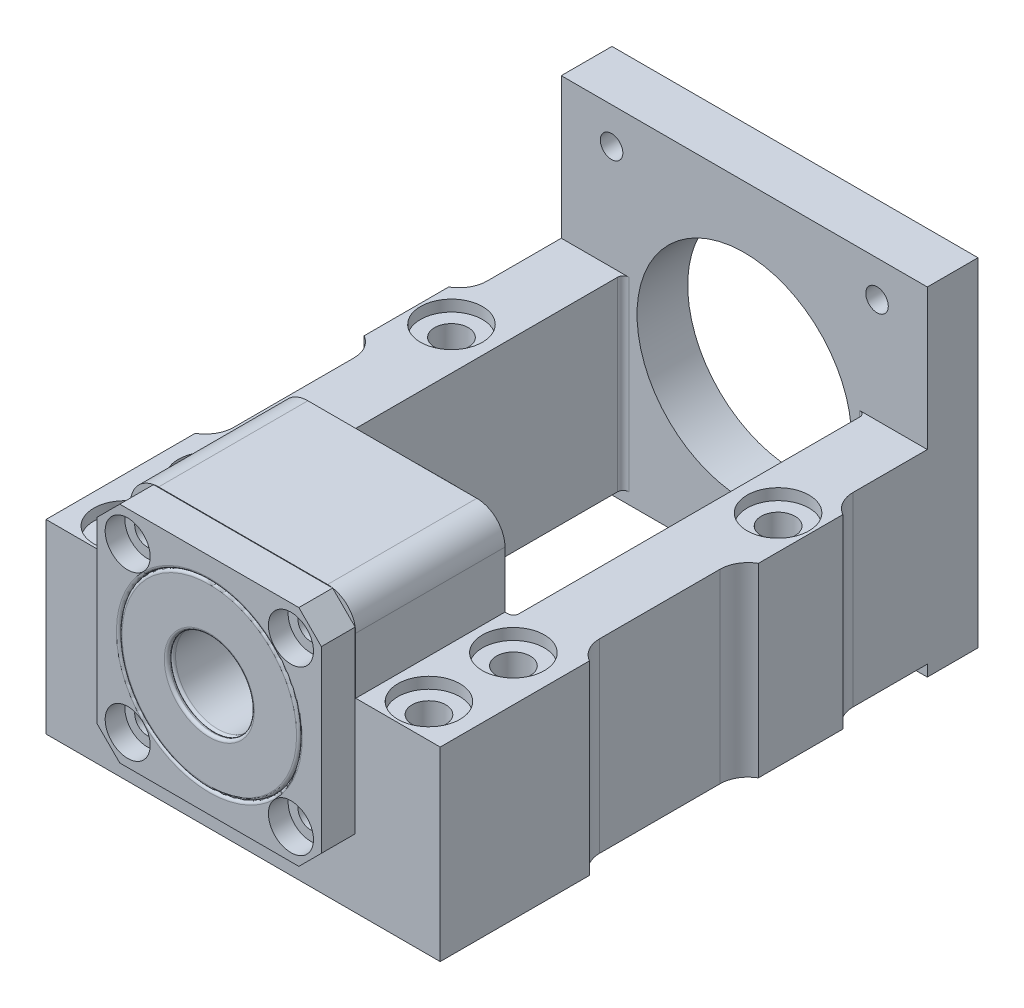
SolidWorks part; units mm, degrees
other "Camera1"
material "Gray Cast Iron"
ref_plane "Front Plane" through (0, 0, 0) normal (0, 0, 1) x (1, 0, 0)
ref_plane "Top Plane" through (0, 0, 0) normal (0, 1, 0) x (1, 0, 0)
ref_plane "Right Plane" through (0, 0, 0) normal (1, 0, 0) x (0, 0, -1)
sketch "Sketch1" plane through (0, 0, 0) normal (0, 0, 1) x (1, 0, 0)
  line L0 (-35, 0) -> (35, 0) construction
  line L1 (0, 0) -> (0, -28) construction
  line L2 (-35, -28) -> (35, -28)
  line L3 (-35, 0) -> (-35, -28)
  line L4 (35, 0) -> (35, -28)
  line L5 (-35, 5) -> (-35, 0)
  line L12 (-35, 5) -> (35, 5)
  line L13 (35, 5) -> (35, 0)
  point P4 (0, 0)
  point P10 (0, -28)
  dimension "D1" = 70
  dimension "D2" = 28
  dimension "D3" = 33
extrude "Boss-Extrude1" add sketch "Sketch1" against normal blind 98
sketch "Sketch2" plane through (0, 5, 0) normal (0, 1, 0) x (1, 0, 0)
  line L0 (0, 98) -> (0, 108.2746) construction
  line L1 (35, 98) -> (-35, 98) construction
  line L2 (-29, 108.2746) -> (29, 108.2746) construction
  line L3 (-29, 108.2746) -> (-29, 66) construction
  line L5 (29, 108.2746) -> (29, 66) construction
  line L6 (-29, 66) -> (29, 66) construction
  line L7 (0, 0) -> (0, -10.7937) construction
  line L8 (-27, -10.7937) -> (27, -10.7937) construction
  line L9 (-27, -10.7937) -> (-27, 21) construction
  line L10 (-27, 21) -> (27, 21) construction
  line L11 (27, 21) -> (27, -10.7937) construction
  line L13 (-27, 6) -> (27, 6) construction
  circle A0 centre (-29, 66) radius 3
  circle A1 centre (29, 66) radius 3
  circle A6 centre (-27, 21) radius 3
  circle A7 centre (-27, 6) radius 3
  circle A8 centre (27, 21) radius 3
  circle A9 centre (27, 6) radius 3
  point P8 (0, 108.2746)
  point P15 (0, -10.7937)
  dimension "D5" = 6
  dimension "D1" = 58
  dimension "D2" = 32
  dimension "D3" = 54
  dimension "D4" = 45
  dimension "D6" = 15
extrude "Cut-Extrude1" cut sketch "Sketch2" against normal blind 50
sketch "Sketch3" plane through (0, 5, 0) normal (0, 1, 0) x (1, 0, 0)
  circle A0 centre (-29, 66) radius 5.5
  circle A1 centre (29, 66) radius 5.5
  circle A6 centre (-27, 21) radius 5.5
  circle A7 centre (-27, 6) radius 5.5
  circle A8 centre (27, 21) radius 5.5
  circle A9 centre (27, 6) radius 5.5
  dimension "D1" = 11
extrude "Cut-Extrude3" cut sketch "Sketch3" against normal blind 2
sketch "Sketch4" plane through (0, 0, -98) normal (0, 0, 1) x (1, 0, 0)
  line L0 (0, -30) -> (0, 30) construction
  line L1 (-32.5, -30) -> (32.5, -30)
  line L2 (-32.5, 30) -> (32.5, 30)
  line L3 (-32.5, 30) -> (-32.5, -30)
  line L4 (32.5, 30) -> (32.5, -30)
  point P4 (0, 0)
  point P7 (0, -30)
  dimension "D1" = 65
  dimension "D2" = 60
extrude "Boss-Extrude3" add sketch "Sketch4" along normal blind 9
sketch "Sketch5" plane through (0, 5, 0) normal (0, 1, 0) x (1, 0, 0)
  line L0 (-21.5, 26.5) -> (21.5, 26.5)
  line L1 (21.5, 26.5) -> (21.5, 89)
  line L2 (32.5, 89) -> (-32.5, 89) construction
  line L3 (-21.5, 26.5) -> (-21.5, 89)
  line L4 (-21.5, 89) -> (21.5, 89)
extrude "Cut-Extrude4" cut sketch "Sketch5" against normal blind 50
sketch "Sketch6" plane through (0, 0, 0) normal (0, 0, 1) x (1, 0, 0)
  line L0 (0, -20) -> (0, 20) construction
  line L1 (-20, 20) -> (20, 20)
  line L2 (-20, 20) -> (-20, -20)
  line L3 (-20, -20) -> (20, -20)
  line L4 (20, -20) -> (20, 20)
  point P4 (0, 0)
  point P8 (0, 20)
  dimension "D1" = 40
  dimension "D2" = 40
extrude "Boss-Extrude4" add sketch "Sketch6" against normal blind 26.5
sketch "Sketch7" plane through (0, 5, 0) normal (0, 1, 0) x (1, 0, 0)
  line L0 (-29, 71.5) -> (29, 71.5) construction
  line L2 (-29, 71.5) -> (-35, 71.5) construction
  line L3 (-35, 98) -> (-35, 0) construction
  line L4 (29, 71.5) -> (35, 71.5) construction
  line L5 (35, 98) -> (35, 0) construction
  line L6 (32.5, 98) -> (32.5, 71.5)
  line L7 (32.5, 71.5) -> (35, 71.5)
  line L8 (35, 71.5) -> (35, 98)
  line L9 (35, 98) -> (32.5, 98)
  line L10 (-35, 98) -> (-35, 71.5)
  line L11 (-35, 98) -> (-32.5, 98)
  line L12 (-32.5, 98) -> (-32.5, 71.5)
  line L13 (-32.5, 71.5) -> (-35, 71.5)
  line L14 (-27, 26.5) -> (27, 26.5) construction
  line L15 (27, 26.5) -> (35, 26.5) construction
  line L16 (-27, 26.5) -> (-35, 26.5) construction
  line L17 (32.5, 26.5) -> (32.5, 56.5)
  line L18 (32.5, 56.5) -> (35, 56.5)
  line L19 (35, 56.5) -> (35, 26.5)
  line L20 (35, 26.5) -> (32.5, 26.5)
  line L21 (-32.5, 26.5) -> (-32.5, 56.5)
  line L22 (-32.5, 56.5) -> (-35, 56.5)
  line L23 (-35, 56.5) -> (-35, 26.5)
  line L24 (-35, 26.5) -> (-32.5, 26.5)
  line L25 (-32.5, 56.5) -> (32.5, 56.5) construction
  circle A0 centre (-29, 66) radius 5.5 construction
  circle A1 centre (-29, 66) radius 5.5 construction
  circle A2 centre (29, 66) radius 5.5 construction
  circle A3 centre (-27, 21) radius 5.5 construction
  circle A4 centre (-27, 21) radius 5.5 construction
  circle A5 centre (27, 21) radius 5.5 construction
  circle A6 centre (27, 21) radius 5.5 construction
  dimension "D1" = 30
extrude "Cut-Extrude5" cut sketch "Sketch7" against normal blind 50
fillet "Fillet1" radius 5 6 edges at (32.5, -11.5, -71.5) (32.5, -11.5, -56.5) (32.5, -11.5, -26.5) (-32.5, -11.5, -26.5) (-32.5, -11.5, -56.5) (-32.5, -11.5, -71.5)
sketch "Sketch8" plane through (0, 0, -98) normal (0, 0, 1) x (1, 0, 0)
  circle A0 centre (0, 0) radius 19.05
  dimension "D1" = 38.1
extrude "Cut-Extrude6" cut sketch "Sketch8" along normal blind 10
sketch "Sketch9" plane through (0, 0, 0) normal (0, 0, 1) x (1, 0, 0)
  line L0 (0, -19.9) -> (0, 19.9) construction
  line L1 (-19.9, 19.9) -> (19.9, 19.9)
  line L2 (-19.9, 19.9) -> (-19.9, -19.9)
  line L3 (-19.9, -19.9) -> (19.9, -19.9)
  line L4 (19.9, -19.9) -> (19.9, 19.9)
  point P4 (0, 0)
  point P8 (0, 19.9)
  dimension "D1" = 39.8
  dimension "D2" = 39.8
extrude "Boss-Extrude5" add sketch "Sketch9" along normal blind 6 separate body
sketch "Sketch10" plane through (0, 0, -26.5) normal (0, 0, 1) x (1, 0, 0)
  circle A0 centre (0, 0) radius 16
  dimension "D1" = 32
extrude "Cut-Extrude7" cut sketch "Sketch10" along normal blind 50
fillet "Fillet2" radius 1 4 edges at (21.5, -11.5, -26.5) (-21.5, -11.5, -26.5) (-21.5, -11.5, -89) (21.5, -11.5, -89)
fillet "Fillet4" radius 0.5 2 edges at (-16, 0, 0) (-16, 0, 6)
sketch "Sketch11" plane through (0, 0, 6) normal (0, 0, 1) x (1, 0, 0)
  circle A0 centre (0, 0) radius 16
  circle A1 centre (0, 0) radius 7.5
  dimension "D1" = 15
extrude "Boss-Extrude6" add sketch "Sketch11" against normal blind 1 separate body
sketch "Sketch12" plane through (0, 0, -26.5) normal (0, 0, 1) x (1, 0, 0)
  circle A0 centre (0, 0) radius 16
  circle A1 centre (0, 0) radius 7.5
  dimension "D1" = 15
extrude "Boss-Extrude7" add sketch "Sketch12" along normal blind 1 separate body
fillet "Fillet5" radius 0.5 3 edges at (7.5, 0, 5) (7.5, 0, 6) (16, 0, 6)
fillet "Fillet6" radius 0.5 1 edges at (16, 0, -26.5)
fillet "Fillet7" radius 0.5 4 edges at (16, 0, -25.5) (7.5, 0, -26.5) (7.5, 0, -25.5) (16, 0, -26.5)
sketch "Sketch13" plane through (0, 0, 5) normal (0, 0, 1) x (1, 0, 0)
  circle A0 centre (0, 0) radius 16
  circle A1 centre (0, 0) radius 7.5
  dimension "D1" = 15
extrude "Boss-Extrude8" add sketch "Sketch13" against normal blind 30.5 separate body
fillet "Fillet8" radius 0.5 2 edges at (7.5, 0, 5) (7.5, 0, -25.5)
sketch "Sketch14" plane through (0, 0, -26.5) normal (0, 0, 1) x (1, 0, 0)
  line L0 (-7.7782, -7.7782) -> (7.7782, 7.7782) construction
  line L5 (-7.7782, 7.7782) -> (7.7782, -7.7782) construction
  line L6 (-15.5563, 0) -> (0, 15.5563)
  line L7 (0, -15.5563) -> (15.5563, 0)
  line L8 (0, 15.5563) -> (15.5563, 0)
  line L9 (-15.5563, 0) -> (0, -15.5563)
  circle A1 centre (0, 0) radius 7.5
  point P5 (0, 0)
  point P8 (0, 0)
  point P11 (-7.7782, 7.7782)
  point P13 (7.7782, -7.7782)
  point P19 (7.7782, 7.7782)
  point P22 (-7.7782, -7.7782)
  dimension "D3" = 15
  dimension "D1" = 22
  dimension "D2" = 22
extrude "Boss-Extrude9" add sketch "Sketch14" against normal blind 8 separate body
chamfer "Chamfer1" distance 5 angle 45 4 edges at (15.5563, 0, -30.5) (0, -15.5563, -30.5) (-15.5563, 0, -30.5) (0, 15.5563, -30.5)
fillet "Fillet9" radius 5 2 edges at (20, 20, -13.25) (-20, 20, -13.25)
chamfer "Chamfer2" distance 4 angle 45 4 edges at (-19.9, -19.9, 3) (19.9, -19.9, 3) (19.9, 19.9, 3) (-19.9, 19.9, 3)
sketch "Sketch15" plane through (0, 0, -98) normal (0, 0, 1) x (1, 0, 0)
  line L0 (0, 0) -> (0, -41.7542) construction
  line L1 (-23.57, -41.7542) -> (23.57, -41.7542) construction
  line L2 (-23.57, -41.7542) -> (-23.57, 23.57) construction
  line L3 (23.57, -41.7542) -> (23.57, 23.57) construction
  line L5 (0, 0) -> (-47.5708, 0) construction
  line L6 (-47.5708, 23.57) -> (-47.5708, -23.57) construction
  line L7 (-47.5708, 23.57) -> (23.57, 23.57) construction
  line L8 (-47.5708, -23.57) -> (23.57, -23.57) construction
  circle A0 centre (-23.57, 23.57) radius 2
  circle A1 centre (-23.57, -23.57) radius 2
  circle A2 centre (23.57, -23.57) radius 2
  circle A3 centre (23.57, 23.57) radius 2
  point P6 (0, -41.7542)
  point P12 (-47.5708, 0)
  dimension "D3" = 4
  dimension "D1" = 47.14
  dimension "D2" = 47.14
extrude "Cut-Extrude8" cut sketch "Sketch15" along normal blind 10
sketch "Sketch16" plane through (0, 0, 6) normal (0, 0, 1) x (1, 0, 0)
  line L0 (0, 0) -> (14.4957, 14.4957) construction
  line L1 (0, 0) -> (-14.4957, -14.4957) construction
  line L2 (0, 0) -> (-14.4957, 14.4957) construction
  line L3 (0, 0) -> (14.4957, -14.4957) construction
  circle A0 centre (0, 0) radius 20.5 construction
  circle A1 centre (14.4957, 14.4957) radius 2.25
  circle A2 centre (-14.4957, 14.4957) radius 2.25
  circle A3 centre (-14.4957, -14.4957) radius 2.25
  circle A4 centre (14.4957, -14.4957) radius 2.25
  dimension "D1" = 41
  dimension "D2" = 4.5
extrude "Cut-Extrude9" cut sketch "Sketch16" against normal blind 6
sketch "Sketch19" plane through (0, 0, 6) normal (0, 0, 1) x (1, 0, 0)
  circle A0 centre (-14.4957, 14.4957) radius 4
  circle A1 centre (14.4957, 14.4957) radius 4
  circle A2 centre (14.4957, -14.4957) radius 4
  circle A3 centre (-14.4957, -14.4957) radius 4
  dimension "D1" = 8
extrude "Cut-Extrude10" cut sketch "Sketch19" against normal blind 3.5
